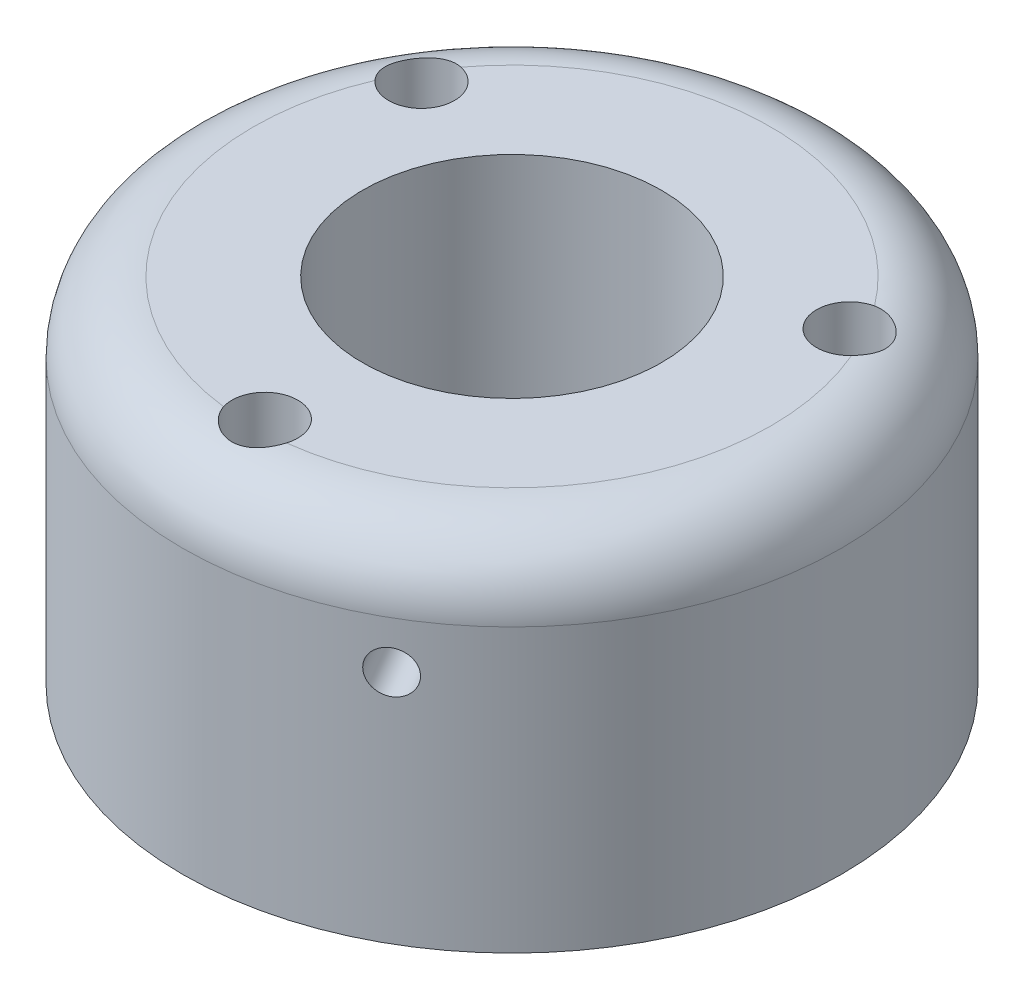
SolidWorks part; units mm, degrees
ref_plane "Front Plane" through (0, 0, 0) normal (0, 0, 1) x (1, 0, 0)
ref_plane "Top Plane" through (0, 0, 0) normal (0, 1, 0) x (1, 0, 0)
ref_plane "Right Plane" through (0, 0, 0) normal (1, 0, 0) x (0, 0, -1)
sketch "Sketch1" plane through (0, 0, 0) normal (0, 1, 0) x (1, 0, 0)
  circle A0 centre (0, 0) radius 14
  dimension "D1" = 28
extrude "Boss-Extrude1" add sketch "Sketch1" along normal blind 15
sketch "Sketch2" plane through (0, 0, 0) normal (0, -1, 0) x (1, 0, 0)
  line L0 (0, 0) -> (0, 14) construction
  line L1 (0, 0) -> (12.1244, -7) construction
  line L2 (0, 0) -> (-12.1244, -7) construction
  line L3 (9.0933, 5.25) -> (0, 0) construction
  circle A1 centre (0, 10.5) radius 1.4
  circle A3 centre (0, 0) radius 14 construction
  circle A4 centre (0, 0) radius 14 construction
  circle A5 centre (0, 0) radius 6.35
  circle A6 centre (9.0933, -5.25) radius 1.4
  circle A7 centre (-9.0933, -5.25) radius 1.4
  point P26 (0, 0)
  dimension "D1" = 2.8
  dimension "D2" = 10.5
  dimension "D3" = 12.7
  dimension "D4" = 120
  dimension "D6" = 2.8
  dimension "D8" = 2.8
  dimension "D9" = 10.5
  dimension "D5" = 120
  dimension "D7" = 10.5
  dimension "D11" = 10.5
  dimension "D12" = 60
extrude "Cut-Extrude1" cut sketch "Sketch2" against normal through all
sketch "Sketch3" plane through (0, 0, 0) normal (0, 1, 0) x (1, 0, 0)
  line L0 (0, 0) -> (9.0933, -5.25)
  line L1 (9.0933, -5.25) -> (0, -10.5)
  line L2 (0, -10.5) -> (0, 0)
  point P7 (9.0933, -5.25)
extrude "Boss-Extrude2" add sketch "Sketch3" against normal blind 2
sketch "Sketch4" plane through (4.5466, 0, 7.875) normal (0.5, 0, 0.866) x (0.866, 0, -0.5)
  line L0 (-5.25, 0) -> (-3.85, 0) construction
  line L1 (-5.25, 0) -> (5.25, 0)
  line L2 (-5.25, 0) -> (-5.25, -2)
  line L3 (-5.25, -2) -> (5.25, -2)
  line L4 (5.25, 0) -> (5.25, -2)
  line L5 (-5.25, -2) -> (-5.25, 0) construction
  line L7 (14, 15) -> (-14, 15) construction
  circle A0 centre (0, 10) radius 0.9
  dimension "D1" = 1.8
  dimension "D2" = 5
extrude "Cut-Extrude2" cut sketch "Sketch4" against normal blind 10 and the other way blind 17
sketch "Sketch5" plane through (0, 0, 0) normal (0, -1, 0) x (1, 0, 0)
  line L0 (0, 0) -> (0, 14) construction
  line L1 (0, 0) -> (9.0933, -5.25) construction
  line L2 (0, 0) -> (9.0933, 5.25) construction
  circle A0 centre (0, 0) radius 10.5 construction
  circle A1 centre (9.0933, 5.25) radius 2.8
  circle A2 centre (0, 0) radius 14 construction
  circle A3 centre (0, -10.5) radius 2.8
  circle A4 centre (-9.0933, 5.25) radius 2.8
  point P18 (0, 0)
  dimension "D2" = 5.6
  dimension "D1" = 60
  dimension "D3" = 3
extrude "Cut-Extrude3" cut sketch "Sketch5" against normal blind 5
fillet "Fillet1" radius 3 1 edges at (0, 15, 14)
